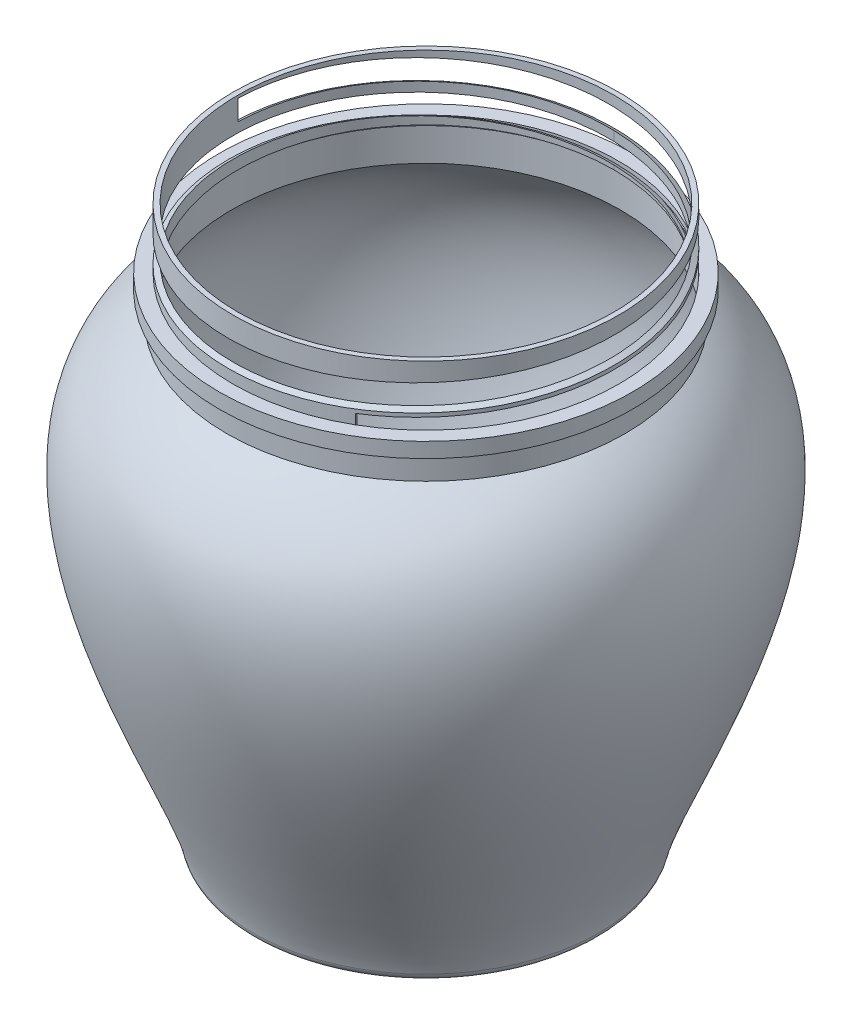
SolidWorks part; units mm, degrees
ref_plane "Přední rovina" through (0, 0, 0) normal (0, 0, 1) x (1, 0, 0)
ref_plane "Horní rovina" through (0, 0, 0) normal (0, 1, 0) x (1, 0, 0)
ref_plane "Pravá rovina" through (0, 0, 0) normal (1, 0, 0) x (0, 0, -1)
sketch "Skica1" plane through (0, 0, 0) normal (0, 0, 1) x (1, 0, 0)
  line L0 (-40, 91) -> (-40, 96)
  line L1 (-40, 96) -> (-41.5, 96)
  line L2 (-41.5, 96) -> (-41.5, 99)
  line L3 (-41.5, 99) -> (-38.75, 99)
  line L4 (-38.75, 99) -> (-38.75, 111)
  line L5 (-38.75, 111) -> (0, 111)
  line L6 (0, -4.8923) -> (0, 114.4078) construction
  line L7 (-34.5, 0) -> (0, 0)
  line L8 (0, 111) -> (0, 0)
  spline S0 degree 3 poles (-34.5, 0) (-36.0449, 15.3057) (-73.4133, 70.9877) (-40, 91) knots 0 0 0 0 1 1 1 1
  dimension "D10" = 69
  dimension "D1" = 80
  dimension "D2" = 5
  dimension "D3" = 3
  dimension "D4" = 83
  dimension "D5" = 77.5
  dimension "D6" = 12
  dimension "D7" = 111
  dimension "D8" = 100
  dimension "D9" = 30
revolve "Rotovat1" add sketch "Skica1" angle 360 about L6
shell "Skořepina15" thickness 1 removed face at (0, 111, -38.75)
thread "Závit1" pitch 6 method cut profile "Profil závitu1" start angle 0, offset 0, length 10, pitch 6, diameter 77.5
ref_plane "Rovina1" through (-38.75, 111, 0) normal (0, 0, 1) x (-1, 0, 0)
sketch "Profil závitu1" plane through (-38.75, 111, 0) normal (0, 0, 1) x (-1, 0, 0)
  line L0 (0, 0) -> (0, 6) construction
  line L11 (0, 0) -> (0, 5.25)
  line L12 (0, 5.25) -> (-3.2476, 3.375)
  line L13 (-3.2476, 3.375) -> (-3.2476, 1.875)
  line L15 (-3.2476, 1.875) -> (0, 0)
  line L17 (-3.2476, 2.625) -> (0, 2.625) construction
  point P2 (0, 0)
  dimension "Pitch" = 6
  dimension "Profile_Angle" = 60
  dimension "Profile_Land" = 1.5
  dimension "Profile_Height" = 3.2476
fillet "Zaoblit1" radius 2 1 edges at (0, 0, -34.5)
sketch "Skica5" plane through (0, 0, 0) normal (0, -1, 0) x (1, 0, 0)
  line L0 (0, 40.455) -> (0, -41.4706) construction
  line L1 (-40.6769, 0) -> (42.8422, 0) construction
  line L2 (0, 31.5) -> (0, 27.5)
  line L3 (0, 27.5) -> (-0.9, 27.5)
  line L4 (-0.9, 27.5) -> (-0.9, 31.5)
  line L5 (-0.9, 31.5) -> (0, 31.5)
  line L6 (1.9779, 31.4378) -> (1.7267, 27.4457)
  line L7 (1.7267, 27.4457) -> (0.8285, 27.5022)
  line L8 (0.8285, 27.5022) -> (1.0797, 31.4944)
  line L9 (1.0797, 31.4944) -> (1.9779, 31.4378)
  line L10 (3.948, 31.2516) -> (3.4467, 27.2832)
  line L11 (3.4467, 27.2832) -> (2.5538, 27.396)
  line L12 (2.5538, 27.396) -> (3.0551, 31.3644)
  line L13 (3.0551, 31.3644) -> (3.948, 31.2516)
  line L14 (5.9025, 30.942) -> (5.153, 27.0129)
  line L15 (5.153, 27.0129) -> (4.2689, 27.1815)
  line L16 (4.2689, 27.1815) -> (5.0185, 31.1107)
  line L17 (5.0185, 31.1107) -> (5.9025, 30.942)
  line L18 (7.8337, 30.5104) -> (6.839, 26.636)
  line L19 (6.839, 26.636) -> (5.9672, 26.8599)
  line L20 (5.9672, 26.8599) -> (6.962, 30.7342)
  line L21 (6.962, 30.7342) -> (7.8337, 30.5104)
  line L22 (9.734, 29.9583) -> (8.498, 26.1541)
  line L23 (8.498, 26.1541) -> (7.642, 26.4322)
  line L24 (7.642, 26.4322) -> (8.8781, 30.2364)
  line L25 (8.8781, 30.2364) -> (9.734, 29.9583)
  line L26 (11.5959, 29.288) -> (10.1234, 25.5689)
  line L27 (10.1234, 25.5689) -> (9.2866, 25.9002)
  line L28 (9.2866, 25.9002) -> (10.7591, 29.6193)
  line L29 (10.7591, 29.6193) -> (11.5959, 29.288)
  line L30 (13.412, 28.5021) -> (11.7089, 24.8827)
  line L31 (11.7089, 24.8827) -> (10.8946, 25.2659)
  line L32 (10.8946, 25.2659) -> (12.5977, 28.8853)
  line L33 (12.5977, 28.8853) -> (13.412, 28.5021)
  line L34 (15.1752, 27.6037) -> (13.2482, 24.0984)
  line L35 (13.2482, 24.0984) -> (12.4596, 24.532)
  line L36 (12.4596, 24.532) -> (14.3866, 28.0372)
  line L37 (14.3866, 28.0372) -> (15.1752, 27.6037)
  line L38 (16.8785, 26.5963) -> (14.7352, 23.219)
  line L39 (14.7352, 23.219) -> (13.9753, 23.7013)
  line L40 (13.9753, 23.7013) -> (16.1186, 27.0786)
  line L41 (16.1186, 27.0786) -> (16.8785, 26.5963)
  line L42 (18.5152, 25.484) -> (16.1641, 22.248)
  line L43 (16.1641, 22.248) -> (15.436, 22.777)
  line L44 (15.436, 22.777) -> (17.7871, 26.013)
  line L45 (17.7871, 26.013) -> (18.5152, 25.484)
  line L46 (20.0789, 24.2712) -> (17.5292, 21.1891)
  line L47 (17.5292, 21.1891) -> (16.8357, 21.7628)
  line L48 (16.8357, 21.7628) -> (19.3854, 24.8448)
  line L49 (19.3854, 24.8448) -> (20.0789, 24.2712)
  line L50 (21.5632, 22.9625) -> (18.825, 20.0466)
  line L51 (18.825, 20.0466) -> (18.169, 20.6627)
  line L52 (18.169, 20.6627) -> (20.9072, 23.5786)
  line L53 (20.9072, 23.5786) -> (21.5632, 22.9625)
  line L54 (22.9625, 21.5632) -> (20.0466, 18.825)
  line L55 (20.0466, 18.825) -> (19.4305, 19.4811)
  line L56 (19.4305, 19.4811) -> (22.3464, 22.2193)
  line L57 (22.3464, 22.2193) -> (22.9625, 21.5632)
  line L58 (24.2712, 20.0789) -> (21.1891, 17.5292)
  line L59 (21.1891, 17.5292) -> (20.6154, 18.2226)
  line L60 (20.6154, 18.2226) -> (23.6975, 20.7723)
  line L61 (23.6975, 20.7723) -> (24.2712, 20.0789)
  line L62 (25.484, 18.5152) -> (22.248, 16.1641)
  line L63 (22.248, 16.1641) -> (21.719, 16.8922)
  line L64 (21.719, 16.8922) -> (24.955, 19.2434)
  line L65 (24.955, 19.2434) -> (25.484, 18.5152)
  line L66 (26.5963, 16.8785) -> (23.219, 14.7352)
  line L67 (23.219, 14.7352) -> (22.7368, 15.4951)
  line L68 (22.7368, 15.4951) -> (26.1141, 17.6384)
  line L69 (26.1141, 17.6384) -> (26.5963, 16.8785)
  line L70 (27.6037, 15.1752) -> (24.0984, 13.2482)
  line L71 (24.0984, 13.2482) -> (23.6649, 14.0369)
  line L72 (23.6649, 14.0369) -> (27.1701, 15.9639)
  line L73 (27.1701, 15.9639) -> (27.6037, 15.1752)
  line L74 (28.5021, 13.412) -> (24.8827, 11.7089)
  line L75 (24.8827, 11.7089) -> (24.4995, 12.5233)
  line L76 (24.4995, 12.5233) -> (28.1189, 14.2264)
  line L77 (28.1189, 14.2264) -> (28.5021, 13.412)
  line L78 (29.288, 11.5959) -> (25.5689, 10.1234)
  line L79 (25.5689, 10.1234) -> (25.2375, 10.9602)
  line L80 (25.2375, 10.9602) -> (28.9566, 12.4327)
  line L81 (28.9566, 12.4327) -> (29.288, 11.5959)
  line L82 (29.9583, 9.734) -> (26.1541, 8.498)
  line L83 (26.1541, 8.498) -> (25.8759, 9.3539)
  line L84 (25.8759, 9.3539) -> (29.6802, 10.59)
  line L85 (29.6802, 10.59) -> (29.9583, 9.734)
  line L86 (30.5104, 7.8337) -> (26.636, 6.839)
  line L87 (26.636, 6.839) -> (26.4122, 7.7107)
  line L88 (26.4122, 7.7107) -> (30.2865, 8.7055)
  line L89 (30.2865, 8.7055) -> (30.5104, 7.8337)
  line L90 (30.942, 5.9025) -> (27.0129, 5.153)
  line L91 (27.0129, 5.153) -> (26.8443, 6.037)
  line L92 (26.8443, 6.037) -> (30.7734, 6.7866)
  line L93 (30.7734, 6.7866) -> (30.942, 5.9025)
  line L94 (31.2516, 3.948) -> (27.2832, 3.4467)
  line L95 (27.2832, 3.4467) -> (27.1704, 4.3396)
  line L96 (27.1704, 4.3396) -> (31.1388, 4.8409)
  line L97 (31.1388, 4.8409) -> (31.2516, 3.948)
  line L98 (31.4378, 1.9779) -> (27.4457, 1.7267)
  line L99 (27.4457, 1.7267) -> (27.3892, 2.625)
  line L100 (27.3892, 2.625) -> (31.3813, 2.8761)
  line L101 (31.3813, 2.8761) -> (31.4378, 1.9779)
  line L102 (31.5, 0) -> (27.5, 0)
  line L103 (27.5, 0) -> (27.5, 0.9)
  line L104 (27.5, 0.9) -> (31.5, 0.9)
  line L105 (31.5, 0.9) -> (31.5, 0)
  line L106 (31.4378, -1.9779) -> (27.4457, -1.7267)
  line L107 (27.4457, -1.7267) -> (27.5022, -0.8285)
  line L108 (27.5022, -0.8285) -> (31.4944, -1.0797)
  line L109 (31.4944, -1.0797) -> (31.4378, -1.9779)
  line L110 (31.2516, -3.948) -> (27.2832, -3.4467)
  line L111 (27.2832, -3.4467) -> (27.396, -2.5538)
  line L112 (27.396, -2.5538) -> (31.3644, -3.0551)
  line L113 (31.3644, -3.0551) -> (31.2516, -3.948)
  line L114 (30.942, -5.9025) -> (27.0129, -5.153)
  line L115 (27.0129, -5.153) -> (27.1815, -4.2689)
  line L116 (27.1815, -4.2689) -> (31.1107, -5.0185)
  line L117 (31.1107, -5.0185) -> (30.942, -5.9025)
  line L118 (30.5104, -7.8337) -> (26.636, -6.839)
  line L119 (26.636, -6.839) -> (26.8599, -5.9672)
  line L120 (26.8599, -5.9672) -> (30.7342, -6.962)
  line L121 (30.7342, -6.962) -> (30.5104, -7.8337)
  line L122 (29.9583, -9.734) -> (26.1541, -8.498)
  line L123 (26.1541, -8.498) -> (26.4322, -7.642)
  line L124 (26.4322, -7.642) -> (30.2364, -8.8781)
  line L125 (30.2364, -8.8781) -> (29.9583, -9.734)
  line L126 (29.288, -11.5959) -> (25.5689, -10.1234)
  line L127 (25.5689, -10.1234) -> (25.9002, -9.2866)
  line L128 (25.9002, -9.2866) -> (29.6193, -10.7591)
  line L129 (29.6193, -10.7591) -> (29.288, -11.5959)
  line L130 (28.5021, -13.412) -> (24.8827, -11.7089)
  line L131 (24.8827, -11.7089) -> (25.2659, -10.8946)
  line L132 (25.2659, -10.8946) -> (28.8853, -12.5977)
  line L133 (28.8853, -12.5977) -> (28.5021, -13.412)
  line L134 (27.6037, -15.1752) -> (24.0984, -13.2482)
  line L135 (24.0984, -13.2482) -> (24.532, -12.4596)
  line L136 (24.532, -12.4596) -> (28.0372, -14.3866)
  line L137 (28.0372, -14.3866) -> (27.6037, -15.1752)
  line L138 (26.5963, -16.8785) -> (23.219, -14.7352)
  line L139 (23.219, -14.7352) -> (23.7013, -13.9753)
  line L140 (23.7013, -13.9753) -> (27.0786, -16.1186)
  line L141 (27.0786, -16.1186) -> (26.5963, -16.8785)
  line L142 (25.484, -18.5152) -> (22.248, -16.1641)
  line L143 (22.248, -16.1641) -> (22.777, -15.436)
  line L144 (22.777, -15.436) -> (26.013, -17.7871)
  line L145 (26.013, -17.7871) -> (25.484, -18.5152)
  line L146 (24.2712, -20.0789) -> (21.1891, -17.5292)
  line L147 (21.1891, -17.5292) -> (21.7628, -16.8357)
  line L148 (21.7628, -16.8357) -> (24.8448, -19.3854)
  line L149 (24.8448, -19.3854) -> (24.2712, -20.0789)
  line L150 (22.9625, -21.5632) -> (20.0466, -18.825)
  line L151 (20.0466, -18.825) -> (20.6627, -18.169)
  line L152 (20.6627, -18.169) -> (23.5786, -20.9072)
  line L153 (23.5786, -20.9072) -> (22.9625, -21.5632)
  line L154 (21.5632, -22.9625) -> (18.825, -20.0466)
  line L155 (18.825, -20.0466) -> (19.4811, -19.4305)
  line L156 (19.4811, -19.4305) -> (22.2193, -22.3464)
  line L157 (22.2193, -22.3464) -> (21.5632, -22.9625)
  line L158 (20.0789, -24.2712) -> (17.5292, -21.1891)
  line L159 (17.5292, -21.1891) -> (18.2226, -20.6154)
  line L160 (18.2226, -20.6154) -> (20.7723, -23.6975)
  line L161 (20.7723, -23.6975) -> (20.0789, -24.2712)
  line L162 (18.5152, -25.484) -> (16.1641, -22.248)
  line L163 (16.1641, -22.248) -> (16.8922, -21.719)
  line L164 (16.8922, -21.719) -> (19.2434, -24.955)
  line L165 (19.2434, -24.955) -> (18.5152, -25.484)
  line L166 (16.8785, -26.5963) -> (14.7352, -23.219)
  line L167 (14.7352, -23.219) -> (15.4951, -22.7368)
  line L168 (15.4951, -22.7368) -> (17.6384, -26.1141)
  line L169 (17.6384, -26.1141) -> (16.8785, -26.5963)
  line L170 (15.1752, -27.6037) -> (13.2482, -24.0984)
  line L171 (13.2482, -24.0984) -> (14.0369, -23.6649)
  line L172 (14.0369, -23.6649) -> (15.9639, -27.1701)
  line L173 (15.9639, -27.1701) -> (15.1752, -27.6037)
  line L174 (13.412, -28.5021) -> (11.7089, -24.8827)
  line L175 (11.7089, -24.8827) -> (12.5233, -24.4995)
  line L176 (12.5233, -24.4995) -> (14.2264, -28.1189)
  line L177 (14.2264, -28.1189) -> (13.412, -28.5021)
  line L178 (11.5959, -29.288) -> (10.1234, -25.5689)
  line L179 (10.1234, -25.5689) -> (10.9602, -25.2375)
  line L180 (10.9602, -25.2375) -> (12.4327, -28.9566)
  line L181 (12.4327, -28.9566) -> (11.5959, -29.288)
  line L182 (9.734, -29.9583) -> (8.498, -26.1541)
  line L183 (8.498, -26.1541) -> (9.3539, -25.8759)
  line L184 (9.3539, -25.8759) -> (10.59, -29.6802)
  line L185 (10.59, -29.6802) -> (9.734, -29.9583)
  line L186 (7.8337, -30.5104) -> (6.839, -26.636)
  line L187 (6.839, -26.636) -> (7.7107, -26.4122)
  line L188 (7.7107, -26.4122) -> (8.7055, -30.2865)
  line L189 (8.7055, -30.2865) -> (7.8337, -30.5104)
  line L190 (5.9025, -30.942) -> (5.153, -27.0129)
  line L191 (5.153, -27.0129) -> (6.037, -26.8443)
  line L192 (6.037, -26.8443) -> (6.7866, -30.7734)
  line L193 (6.7866, -30.7734) -> (5.9025, -30.942)
  line L194 (3.948, -31.2516) -> (3.4467, -27.2832)
  line L195 (3.4467, -27.2832) -> (4.3396, -27.1704)
  line L196 (4.3396, -27.1704) -> (4.8409, -31.1388)
  line L197 (4.8409, -31.1388) -> (3.948, -31.2516)
  line L198 (1.9779, -31.4378) -> (1.7267, -27.4457)
  line L199 (1.7267, -27.4457) -> (2.625, -27.3892)
  line L200 (2.625, -27.3892) -> (2.8761, -31.3813)
  line L201 (2.8761, -31.3813) -> (1.9779, -31.4378)
  line L202 (0, -31.5) -> (0, -27.5)
  line L203 (0, -27.5) -> (0.9, -27.5)
  line L204 (0.9, -27.5) -> (0.9, -31.5)
  line L205 (0.9, -31.5) -> (0, -31.5)
  line L206 (-1.9779, -31.4378) -> (-1.7267, -27.4457)
  line L207 (-1.7267, -27.4457) -> (-0.8285, -27.5022)
  line L208 (-0.8285, -27.5022) -> (-1.0797, -31.4944)
  line L209 (-1.0797, -31.4944) -> (-1.9779, -31.4378)
  line L210 (-3.948, -31.2516) -> (-3.4467, -27.2832)
  line L211 (-3.4467, -27.2832) -> (-2.5538, -27.396)
  line L212 (-2.5538, -27.396) -> (-3.0551, -31.3644)
  line L213 (-3.0551, -31.3644) -> (-3.948, -31.2516)
  line L214 (-5.9025, -30.942) -> (-5.153, -27.0129)
  line L215 (-5.153, -27.0129) -> (-4.2689, -27.1815)
  line L216 (-4.2689, -27.1815) -> (-5.0185, -31.1107)
  line L217 (-5.0185, -31.1107) -> (-5.9025, -30.942)
  line L218 (-7.8337, -30.5104) -> (-6.839, -26.636)
  line L219 (-6.839, -26.636) -> (-5.9672, -26.8599)
  line L220 (-5.9672, -26.8599) -> (-6.962, -30.7342)
  line L221 (-6.962, -30.7342) -> (-7.8337, -30.5104)
  line L222 (-9.734, -29.9583) -> (-8.498, -26.1541)
  line L223 (-8.498, -26.1541) -> (-7.642, -26.4322)
  line L224 (-7.642, -26.4322) -> (-8.8781, -30.2364)
  line L225 (-8.8781, -30.2364) -> (-9.734, -29.9583)
  line L226 (-11.5959, -29.288) -> (-10.1234, -25.5689)
  line L227 (-10.1234, -25.5689) -> (-9.2866, -25.9002)
  line L228 (-9.2866, -25.9002) -> (-10.7591, -29.6193)
  line L229 (-10.7591, -29.6193) -> (-11.5959, -29.288)
  line L230 (-13.412, -28.5021) -> (-11.7089, -24.8827)
  line L231 (-11.7089, -24.8827) -> (-10.8946, -25.2659)
  line L232 (-10.8946, -25.2659) -> (-12.5977, -28.8853)
  line L233 (-12.5977, -28.8853) -> (-13.412, -28.5021)
  line L234 (-15.1752, -27.6037) -> (-13.2482, -24.0984)
  line L235 (-13.2482, -24.0984) -> (-12.4596, -24.532)
  line L236 (-12.4596, -24.532) -> (-14.3866, -28.0372)
  line L237 (-14.3866, -28.0372) -> (-15.1752, -27.6037)
  line L238 (-16.8785, -26.5963) -> (-14.7352, -23.219)
  line L239 (-14.7352, -23.219) -> (-13.9753, -23.7013)
  line L240 (-13.9753, -23.7013) -> (-16.1186, -27.0786)
  line L241 (-16.1186, -27.0786) -> (-16.8785, -26.5963)
  line L242 (-18.5152, -25.484) -> (-16.1641, -22.248)
  line L243 (-16.1641, -22.248) -> (-15.436, -22.777)
  line L244 (-15.436, -22.777) -> (-17.7871, -26.013)
  line L245 (-17.7871, -26.013) -> (-18.5152, -25.484)
  line L246 (-20.0789, -24.2712) -> (-17.5292, -21.1891)
  line L247 (-17.5292, -21.1891) -> (-16.8357, -21.7628)
  line L248 (-16.8357, -21.7628) -> (-19.3854, -24.8448)
  line L249 (-19.3854, -24.8448) -> (-20.0789, -24.2712)
  line L250 (-21.5632, -22.9625) -> (-18.825, -20.0466)
  line L251 (-18.825, -20.0466) -> (-18.169, -20.6627)
  line L252 (-18.169, -20.6627) -> (-20.9072, -23.5786)
  line L253 (-20.9072, -23.5786) -> (-21.5632, -22.9625)
  line L254 (-22.9625, -21.5632) -> (-20.0466, -18.825)
  line L255 (-20.0466, -18.825) -> (-19.4305, -19.4811)
  line L256 (-19.4305, -19.4811) -> (-22.3464, -22.2193)
  line L257 (-22.3464, -22.2193) -> (-22.9625, -21.5632)
  line L258 (-24.2712, -20.0789) -> (-21.1891, -17.5292)
  line L259 (-21.1891, -17.5292) -> (-20.6154, -18.2226)
  line L260 (-20.6154, -18.2226) -> (-23.6975, -20.7723)
  line L261 (-23.6975, -20.7723) -> (-24.2712, -20.0789)
  line L262 (-25.484, -18.5152) -> (-22.248, -16.1641)
  line L263 (-22.248, -16.1641) -> (-21.719, -16.8922)
  line L264 (-21.719, -16.8922) -> (-24.955, -19.2434)
  line L265 (-24.955, -19.2434) -> (-25.484, -18.5152)
  line L266 (-26.5963, -16.8785) -> (-23.219, -14.7352)
  line L267 (-23.219, -14.7352) -> (-22.7368, -15.4951)
  line L268 (-22.7368, -15.4951) -> (-26.1141, -17.6384)
  line L269 (-26.1141, -17.6384) -> (-26.5963, -16.8785)
  line L270 (-27.6037, -15.1752) -> (-24.0984, -13.2482)
  line L271 (-24.0984, -13.2482) -> (-23.6649, -14.0369)
  line L272 (-23.6649, -14.0369) -> (-27.1701, -15.9639)
  line L273 (-27.1701, -15.9639) -> (-27.6037, -15.1752)
  line L274 (-28.5021, -13.412) -> (-24.8827, -11.7089)
  line L275 (-24.8827, -11.7089) -> (-24.4995, -12.5233)
  line L276 (-24.4995, -12.5233) -> (-28.1189, -14.2264)
  line L277 (-28.1189, -14.2264) -> (-28.5021, -13.412)
  line L278 (-29.288, -11.5959) -> (-25.5689, -10.1234)
  line L279 (-25.5689, -10.1234) -> (-25.2375, -10.9602)
  line L280 (-25.2375, -10.9602) -> (-28.9566, -12.4327)
  line L281 (-28.9566, -12.4327) -> (-29.288, -11.5959)
  line L282 (-29.9583, -9.734) -> (-26.1541, -8.498)
  line L283 (-26.1541, -8.498) -> (-25.8759, -9.3539)
  line L284 (-25.8759, -9.3539) -> (-29.6802, -10.59)
  line L285 (-29.6802, -10.59) -> (-29.9583, -9.734)
  line L286 (-30.5104, -7.8337) -> (-26.636, -6.839)
  line L287 (-26.636, -6.839) -> (-26.4122, -7.7107)
  line L288 (-26.4122, -7.7107) -> (-30.2865, -8.7055)
  line L289 (-30.2865, -8.7055) -> (-30.5104, -7.8337)
  line L290 (-30.942, -5.9025) -> (-27.0129, -5.153)
  line L291 (-27.0129, -5.153) -> (-26.8443, -6.037)
  line L292 (-26.8443, -6.037) -> (-30.7734, -6.7866)
  line L293 (-30.7734, -6.7866) -> (-30.942, -5.9025)
  line L294 (-31.2516, -3.948) -> (-27.2832, -3.4467)
  line L295 (-27.2832, -3.4467) -> (-27.1704, -4.3396)
  line L296 (-27.1704, -4.3396) -> (-31.1388, -4.8409)
  line L297 (-31.1388, -4.8409) -> (-31.2516, -3.948)
  line L298 (-31.4378, -1.9779) -> (-27.4457, -1.7267)
  line L299 (-27.4457, -1.7267) -> (-27.3892, -2.625)
  line L300 (-27.3892, -2.625) -> (-31.3813, -2.8761)
  line L301 (-31.3813, -2.8761) -> (-31.4378, -1.9779)
  line L302 (-31.5, 0) -> (-27.5, 0)
  line L303 (-27.5, 0) -> (-27.5, -0.9)
  line L304 (-27.5, -0.9) -> (-31.5, -0.9)
  line L305 (-31.5, -0.9) -> (-31.5, 0)
  line L306 (-31.4378, 1.9779) -> (-27.4457, 1.7267)
  line L307 (-27.4457, 1.7267) -> (-27.5022, 0.8285)
  line L308 (-27.5022, 0.8285) -> (-31.4944, 1.0797)
  line L309 (-31.4944, 1.0797) -> (-31.4378, 1.9779)
  line L310 (-31.2516, 3.948) -> (-27.2832, 3.4467)
  line L311 (-27.2832, 3.4467) -> (-27.396, 2.5538)
  line L312 (-27.396, 2.5538) -> (-31.3644, 3.0551)
  line L313 (-31.3644, 3.0551) -> (-31.2516, 3.948)
  line L314 (-30.942, 5.9025) -> (-27.0129, 5.153)
  line L315 (-27.0129, 5.153) -> (-27.1815, 4.2689)
  line L316 (-27.1815, 4.2689) -> (-31.1107, 5.0185)
  line L317 (-31.1107, 5.0185) -> (-30.942, 5.9025)
  line L318 (-30.5104, 7.8337) -> (-26.636, 6.839)
  line L319 (-26.636, 6.839) -> (-26.8599, 5.9672)
  line L320 (-26.8599, 5.9672) -> (-30.7342, 6.962)
  line L321 (-30.7342, 6.962) -> (-30.5104, 7.8337)
  line L322 (-29.9583, 9.734) -> (-26.1541, 8.498)
  line L323 (-26.1541, 8.498) -> (-26.4322, 7.642)
  line L324 (-26.4322, 7.642) -> (-30.2364, 8.8781)
  line L325 (-30.2364, 8.8781) -> (-29.9583, 9.734)
  line L326 (-29.288, 11.5959) -> (-25.5689, 10.1234)
  line L327 (-25.5689, 10.1234) -> (-25.9002, 9.2866)
  line L328 (-25.9002, 9.2866) -> (-29.6193, 10.7591)
  line L329 (-29.6193, 10.7591) -> (-29.288, 11.5959)
  line L330 (-28.5021, 13.412) -> (-24.8827, 11.7089)
  line L331 (-24.8827, 11.7089) -> (-25.2659, 10.8946)
  line L332 (-25.2659, 10.8946) -> (-28.8853, 12.5977)
  line L333 (-28.8853, 12.5977) -> (-28.5021, 13.412)
  line L334 (-27.6037, 15.1752) -> (-24.0984, 13.2482)
  line L335 (-24.0984, 13.2482) -> (-24.532, 12.4596)
  line L336 (-24.532, 12.4596) -> (-28.0372, 14.3866)
  line L337 (-28.0372, 14.3866) -> (-27.6037, 15.1752)
  line L338 (-26.5963, 16.8785) -> (-23.219, 14.7352)
  line L339 (-23.219, 14.7352) -> (-23.7013, 13.9753)
  line L340 (-23.7013, 13.9753) -> (-27.0786, 16.1186)
  line L341 (-27.0786, 16.1186) -> (-26.5963, 16.8785)
  line L342 (-25.484, 18.5152) -> (-22.248, 16.1641)
  line L343 (-22.248, 16.1641) -> (-22.777, 15.436)
  line L344 (-22.777, 15.436) -> (-26.013, 17.7871)
  line L345 (-26.013, 17.7871) -> (-25.484, 18.5152)
  line L346 (-24.2712, 20.0789) -> (-21.1891, 17.5292)
  line L347 (-21.1891, 17.5292) -> (-21.7628, 16.8357)
  line L348 (-21.7628, 16.8357) -> (-24.8448, 19.3854)
  line L349 (-24.8448, 19.3854) -> (-24.2712, 20.0789)
  line L350 (-22.9625, 21.5632) -> (-20.0466, 18.825)
  line L351 (-20.0466, 18.825) -> (-20.6627, 18.169)
  line L352 (-20.6627, 18.169) -> (-23.5786, 20.9072)
  line L353 (-23.5786, 20.9072) -> (-22.9625, 21.5632)
  line L354 (-21.5632, 22.9625) -> (-18.825, 20.0466)
  line L355 (-18.825, 20.0466) -> (-19.4811, 19.4305)
  line L356 (-19.4811, 19.4305) -> (-22.2193, 22.3464)
  line L357 (-22.2193, 22.3464) -> (-21.5632, 22.9625)
  line L358 (-20.0789, 24.2712) -> (-17.5292, 21.1891)
  line L359 (-17.5292, 21.1891) -> (-18.2226, 20.6154)
  line L360 (-18.2226, 20.6154) -> (-20.7723, 23.6975)
  line L361 (-20.7723, 23.6975) -> (-20.0789, 24.2712)
  line L362 (-18.5152, 25.484) -> (-16.1641, 22.248)
  line L363 (-16.1641, 22.248) -> (-16.8922, 21.719)
  line L364 (-16.8922, 21.719) -> (-19.2434, 24.955)
  line L365 (-19.2434, 24.955) -> (-18.5152, 25.484)
  line L366 (-16.8785, 26.5963) -> (-14.7352, 23.219)
  line L367 (-14.7352, 23.219) -> (-15.4951, 22.7368)
  line L368 (-15.4951, 22.7368) -> (-17.6384, 26.1141)
  line L369 (-17.6384, 26.1141) -> (-16.8785, 26.5963)
  line L370 (-15.1752, 27.6037) -> (-13.2482, 24.0984)
  line L371 (-13.2482, 24.0984) -> (-14.0369, 23.6649)
  line L372 (-14.0369, 23.6649) -> (-15.9639, 27.1701)
  line L373 (-15.9639, 27.1701) -> (-15.1752, 27.6037)
  line L374 (-13.412, 28.5021) -> (-11.7089, 24.8827)
  line L375 (-11.7089, 24.8827) -> (-12.5233, 24.4995)
  line L376 (-12.5233, 24.4995) -> (-14.2264, 28.1189)
  line L377 (-14.2264, 28.1189) -> (-13.412, 28.5021)
  line L378 (-11.5959, 29.288) -> (-10.1234, 25.5689)
  line L379 (-10.1234, 25.5689) -> (-10.9602, 25.2375)
  line L380 (-10.9602, 25.2375) -> (-12.4327, 28.9566)
  line L381 (-12.4327, 28.9566) -> (-11.5959, 29.288)
  line L382 (-9.734, 29.9583) -> (-8.498, 26.1541)
  line L383 (-8.498, 26.1541) -> (-9.3539, 25.8759)
  line L384 (-9.3539, 25.8759) -> (-10.59, 29.6802)
  line L385 (-10.59, 29.6802) -> (-9.734, 29.9583)
  line L386 (-7.8337, 30.5104) -> (-6.839, 26.636)
  line L387 (-6.839, 26.636) -> (-7.7107, 26.4122)
  line L388 (-7.7107, 26.4122) -> (-8.7055, 30.2865)
  line L389 (-8.7055, 30.2865) -> (-7.8337, 30.5104)
  line L390 (-5.9025, 30.942) -> (-5.153, 27.0129)
  line L391 (-5.153, 27.0129) -> (-6.037, 26.8443)
  line L392 (-6.037, 26.8443) -> (-6.7866, 30.7734)
  line L393 (-6.7866, 30.7734) -> (-5.9025, 30.942)
  line L394 (-3.948, 31.2516) -> (-3.4467, 27.2832)
  line L395 (-3.4467, 27.2832) -> (-4.3396, 27.1704)
  line L396 (-4.3396, 27.1704) -> (-4.8409, 31.1388)
  line L397 (-4.8409, 31.1388) -> (-3.948, 31.2516)
  line L398 (-1.9779, 31.4378) -> (-1.7267, 27.4457)
  line L399 (-1.7267, 27.4457) -> (-2.625, 27.3892)
  line L400 (-2.625, 27.3892) -> (-2.8761, 31.3813)
  line L401 (-2.8761, 31.3813) -> (-1.9779, 31.4378)
  point P408 (0, 0)
  dimension "D1" = 0.9
  dimension "D2" = 4
  dimension "D3" = 55
  dimension "D4" = 100
